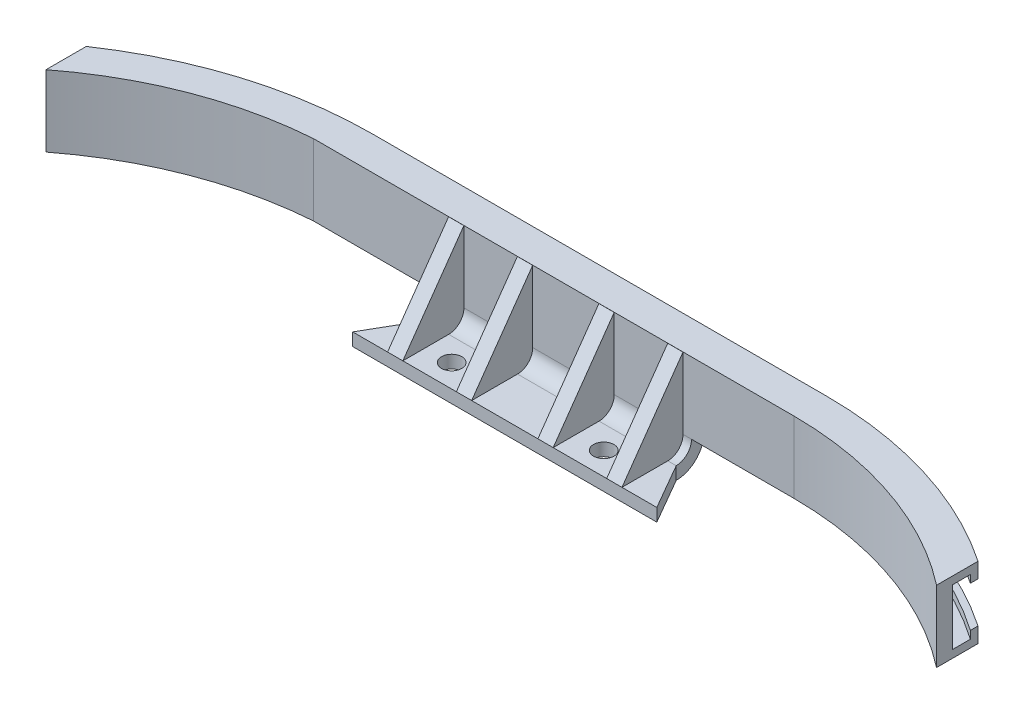
SolidWorks part; units mm, degrees
ref_plane "Front Plane" through (0, 0, 0) normal (0, 0, 1) x (1, 0, 0)
ref_plane "Top Plane" through (0, 0, 0) normal (0, 1, 0) x (1, 0, 0)
ref_plane "Right Plane" through (0, 0, 0) normal (1, 0, 0) x (0, 0, -1)
sketch "Sketch1" plane through (0, 0, 0) normal (0, 1, 0) x (1, 0, 0)
  line L0 (-46.3551, 0) -> (52.009, 0) construction
  line L1 (0, 44.5533) -> (0, -62.175) construction
  line L2 (-29.8412, 0) -> (-24.645, 9)
  line L3 (29.8412, 0) -> (24.645, 9)
  line L4 (-24.645, 9) -> (24.645, 9)
  line L11 (-29.8412, 0) -> (29.8412, 0)
  line L13 (-40.4127, 4.5) -> (37.6406, 4.5) construction
  circle A0 centre (-14.92, 4.5) radius 2
  circle A1 centre (14.92, 4.5) radius 2
  dimension "D9" = 4
  dimension "D10" = 4
  dimension "D1" = 60
  dimension "D2" = 49.29
  dimension "D3" = 9
  dimension "D6" = 4.5
  dimension "D7" = 14.92
  dimension "D8" = 14.92
extrude "Boss-Extrude1" add sketch "Sketch1" along normal blind 2.5 contours L2 L11 L3 L4 A1 A0 | L4 region at (0, 0, -4.3492)
sketch "Sketch3" plane through (0, 0, 0) normal (1, 0, 0) x (0, 0, -1)
  line L0 (9, -3.8455) -> (9, 6.248) construction
  line L1 (9, 2.5) -> (9, 0) construction
  line L2 (9, 0) -> (9, 2.5)
  line L3 (12, 5.5) -> (14.5, 5.5)
  arc A0 (9, 0) -> (14.5, 5.5) centre (9, 5.5) ccw
  arc A1 (9, 2.5) -> (12, 5.5) centre (9, 5.5) ccw
  dimension "D1" = 3
  dimension "D2" = 2.5
extrude "Boss-Extrude2" add sketch "Sketch3" along normal up to vertex (24.645 mm away) and the other way up to vertex (24.645 mm away) up to point (24.645, 2.5, -9) other way up to point (-24.645, 2.5, -9)
sketch "Sketch4" plane through (0, 5.5, 0) normal (0, 1, 0) x (1, 0, 0)
  line L0 (87.5, 12) -> (-87.5, 12) construction
  line L1 (87.5, 12) -> (87.5, -58) construction
  line L2 (0, -21.0924) -> (0, 56.245) construction
  line L3 (70.1134, -16.5214) -> (-66.0404, -16.5214) construction
  line L4 (87.5, -58) -> (-87.5, -58) construction
  line L5 (-87.5, 12) -> (-87.5, -58) construction
  line L6 (44.7959, 12) -> (-49.5586, 12)
  line L7 (-44.7938, 14.5) -> (44.7832, 14.5)
  line L8 (24.645, 14.5) -> (-24.645, 14.5) construction
  line L9 (-87.5, -2.533) -> (-87.5, 0.3724)
  line L10 (87.5, -2.7633) -> (87.5, 0.3723)
  line L11 (-87.5, 3.8724) -> (-87.5, 5.3724)
  line L12 (87.5, 3.8723) -> (87.5, 5.3723)
  line L13 (24.645, 12) -> (-24.645, 12) construction
  line L14 (-44.5, 18.5837) -> (44.5, 18.5836)
  line L15 (-87.5, 5.3724) -> (-87.5, 0.3724)
  line L16 (87.5, 0.3723) -> (87.5, 5.3723)
  line L17 (-44.5, 17.3472) -> (44.5, 17.3471)
  arc A0 (44.7959, 12) -> (87.5, -2.7633) centre (44.5, -58) cw
  arc A1 (-49.5586, 12) -> (-87.5, -2.533) centre (-44.5, -58) ccw
  arc A2 (44.7832, 14.5) -> (87.5, 0.3723) centre (44.5, -58) cw
  arc A3 (-44.7938, 14.5) -> (-87.5, 0.3724) centre (-44.5, -58) ccw
  arc A4 (-87.5, 5.3724) -> (-44.5, 18.5837) centre (-44.5, -58) cw
  arc A5 (87.5, 5.3723) -> (44.5, 18.5836) centre (44.5, -58) ccw
  arc A6 (-87.5, 3.8724) -> (-44.5, 17.3472) centre (-44.5, -58) cw
  arc A7 (87.5, 3.8723) -> (44.5, 17.3471) centre (44.5, -58) ccw
  point P3 (0, 12)
  point P19 (-0.0053, 14.5)
  line M6 (24.645, 14.5) -> (-24.645, 14.5)
  line M7 (-24.645, 14.5) -> (-24.645, 12)
  line M8 (-24.645, 12) -> (24.645, 12)
  line M9 (24.645, 12) -> (24.645, 14.5)
  dimension "D5" = 72.5006
  dimension "D6" = 70.1825
  dimension "D7" = 70.0006
  dimension "D8" = 72.5006
  dimension "D1" = 175
  dimension "D2" = 43
  dimension "D3" = 43
  dimension "D4" = 70
  dimension "D9" = 5
  dimension "D10" = 5
  dimension "D11" = 1.5
  dimension "D12" = 1.5
extrude "Boss-Extrude4" add sketch "Sketch4" along normal blind 14 contours L7 A3 L9 A1 L6 M7 | M9 M6 M7 M8 | A2 L7 L6 A0 L10 M9 region at (34.7205, 5.5, -12.6518) region at (0, 5.5, -13.25) region at (-37.1018, 5.5, -12.6512)
extrude "Boss-Extrude6" add sketch "Sketch4<4>" along normal blind 1.5 contours L16 A7 L17 A6 L15 A3 L7 A2 M6 | A7 L12 A5 L14 A4 L11 A6 L17 region at (67.8173, 5.5, -12.503) region at (67.0835, 5.5, -14.0671)
sketch "Sketch4<4>" plane through (0, 5.5, 0) normal (0, 1, 0) x (1, 0, 0) same geometry as "Sketch4"
extrude "Boss-Extrude7" add sketch "Sketch4<5>" against normal blind 1.5 from surface contours L16 A7 L17 A6 L15 A3 L7 A2 M6 | A7 L12 A5 L14 A4 L11 A6 L17 region at (67.8173, 5.5, -12.503) region at (67.0835, 5.5, -14.0671) starting at face at (-0.578, 19.5, -7.6985)
sketch "Sketch4<5>" plane through (0, 5.5, 0) normal (0, 1, 0) x (1, 0, 0) same geometry as "Sketch4"
extrude "Boss-Extrude8" add sketch "Sketch4<6>" along normal blind 1.5 from surface contours A7 L12 A5 L14 A4 L11 A6 L17 region at (67.0835, 5.5, -14.0671) starting at face at (-0.0013, 7, -11.3634)
sketch "Sketch4<6>" plane through (0, 5.5, 0) normal (0, 1, 0) x (1, 0, 0) same geometry as "Sketch4"
extrude "Boss-Extrude9" add sketch "Sketch4<8>" against normal blind 1.5 from surface contours A7 L12 A5 L14 A4 L11 A6 L17 region at (67.0835, 5.5, -14.0671) starting at face at (-0.0013, 18, -11.3634)
sketch "Sketch4<8>" plane through (0, 5.5, 0) normal (0, 1, 0) x (1, 0, 0) same geometry as "Sketch4"
sketch "Sketch5" plane through (0, 0, 0) normal (1, 0, 0) x (0, 0, -1)
  line L0 (11.978, 19.5) -> (0, 2.5)
  line L1 (18.5836, 19.5) -> (5.3723, 19.5) construction
  line L2 (0, 2.5) -> (9, 2.5)
  line L3 (11.978, 19.5) -> (11.978, 5.5)
  line L4 (5.3723, 5.5) -> (18.5836, 5.5) construction
  arc A0 (11.978, 5.5) -> (9, 2.5) centre (9, 5.4781) cw
  point P12 (0, 0)
extrude "Boss-Extrude10" add sketch "Sketch5" along normal blind 3 from offset 6.5
extrude "Boss-Extrude11" add sketch "Sketch5<3>" along normal blind 3 from offset 20
sketch "Sketch5<3>" plane through (0, 0, 0) normal (1, 0, 0) x (0, 0, -1) same geometry as "Sketch5"
mirror "Mirror1" about plane through (0, 0, 0) normal (1, 0, 0) of "Boss-Extrude10", "Boss-Extrude11"
